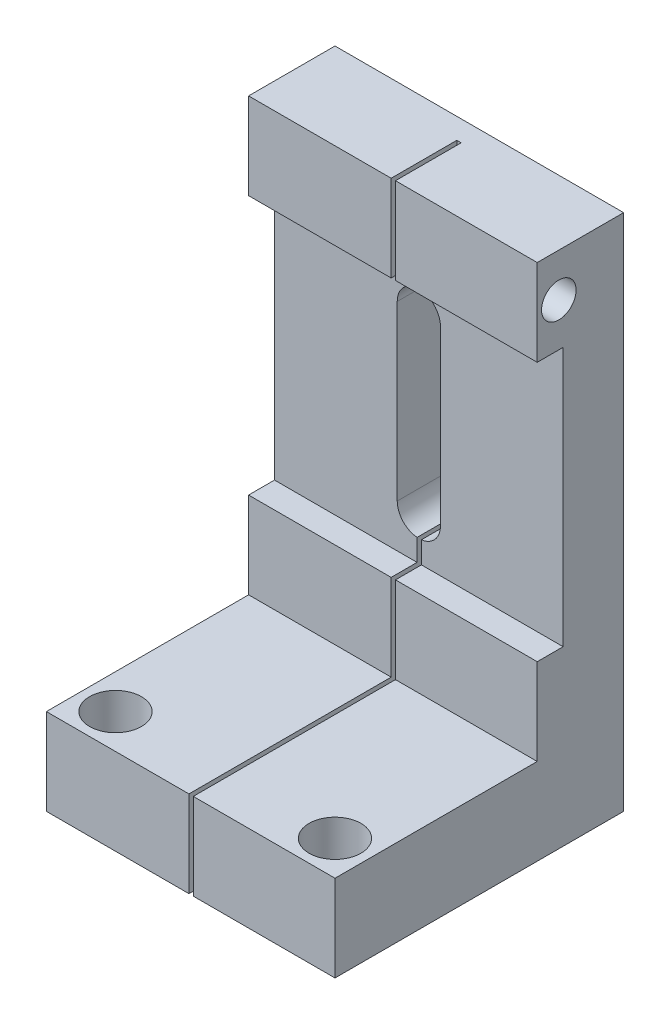
SolidWorks part; units mm, degrees
ref_plane "Front Plane" through (0, 0, 0) normal (0, 0, 1) x (1, 0, 0)
ref_plane "Top Plane" through (0, 0, 0) normal (0, 1, 0) x (1, 0, 0)
ref_plane "Right Plane" through (0, 0, 0) normal (1, 0, 0) x (0, 0, -1)
sketch "Sketch1" plane through (0, 0, 0) normal (0, 0, 1) x (1, 0, 0)
  line L1 (0, 0) -> (-33.4, 0)
  line L2 (0, 0) -> (0, -60)
  line L3 (0, -60) -> (-33.4, -60)
  line L4 (-33.4, 0) -> (-33.4, -60)
  dimension "D1" = 33.4
  dimension "D2" = 60
extrude "Boss-Extrude1" add sketch "Sketch1" along normal blind 10
sketch "Sketch2" plane through (0, 0, 10) normal (0, 0, 1) x (1, 0, 0)
  line L0 (-16.7, -15) -> (-16.7, -35) construction
  line L1 (-14.2, -15) -> (-14.2, -35)
  line L2 (-19.2, -15) -> (-19.2, -35)
  line L3 (0, -60) -> (0, 0) construction
  line L4 (-33.4, -60) -> (0, -60) construction
  arc A0 (-14.2, -15) -> (-19.2, -15) centre (-16.7, -15) ccw
  arc A1 (-19.2, -35) -> (-14.2, -35) centre (-16.7, -35) ccw
  point P2 (-16.7, -25)
  dimension "D1" = 5
  dimension "D2" = 20
  dimension "D3" = 16.7
  dimension "D4" = 35
extrude "Cut-Extrude1" cut sketch "Sketch2" against normal through all
sketch "Sketch5" plane through (0, 0, 0) normal (1, 0, 0) x (0, 0, -1)
  line L0 (-7, -10) -> (-10, -10)
  line L1 (-10, -60) -> (-10, 0) construction
  line L2 (-7, -10) -> (-7, -40)
  line L3 (-10, -60) -> (0, -60) construction
  line L4 (-7, -40) -> (-10, -40)
  line L7 (-10, -10) -> (-10, -40)
  dimension "D1" = 3
  dimension "D4" = 30
  dimension "D5" = 20
extrude "Cut-Extrude4" cut sketch "Sketch5" against normal through all
sketch "Sketch6" plane through (0, 0, 10) normal (0, 0, 1) x (1, 0, 0)
  line L0 (-33.4, -40) -> (-33.4, -60) construction
  line L1 (0, -60) -> (-33.4, -60)
  line L2 (0, -60) -> (0, -50)
  line L3 (0, -50) -> (-33.4, -50)
  line L4 (-33.4, -60) -> (-33.4, -50)
  dimension "D1" = 10
extrude "Boss-Extrude2" add sketch "Sketch6" along normal blind 23.4
sketch "Sketch7" plane through (0, -50, 0) normal (0, 1, 0) x (1, 0, 0)
  line L3 (-33.4, -33.4) -> (-33.4, -10) construction
  circle A0 centre (2.475, -15.1829) radius 2
  circle A1 centre (-29.275, -15.1829) radius 2
  dimension "D1" = 4
  dimension "D2" = 4
  dimension "D3" = 4.125
  dimension "D5" = 31.75
extrude "Cut-Extrude5" [suppressed] cut sketch "Sketch7" against normal blind 40
sketch "Sketch8" plane through (0, 0, 0) normal (0, 1, 0) x (1, 0, 0)
  line L2 (-16.9, -33.4) -> (-16.4, -33.4)
  line L5 (-16.9, -33.4) -> (-16.9, -2.4)
  line L7 (0, -33.4) -> (-33.4, -33.4) construction
  line L9 (-16.9, -2.4) -> (-16.4, -2.4)
  line L10 (-16.4, -33.4) -> (-16.4, -2.4)
  line L11 (-19.2, 0) -> (-19.2, -7) construction
  dimension "D1" = 0.5
  dimension "D2" = 2.3
  dimension "D3" = 31
extrude "Cut-Extrude7" cut sketch "Sketch8" against normal up to surface (60 mm away) up to face at (-16.7, -60, 16.7)
sketch "Sketch9" plane through (0, -60, 0) normal (0, -1, 0) x (1, 0, 0)
  line L3 (0, 33.4) -> (0, 0) construction
  line L5 (-33.4, 7) -> (-16.9, 7) construction
  circle A0 centre (-32.7, 5) radius 2
  circle A1 centre (-7.3, 5) radius 2
  dimension "D1" = 4
  dimension "D3" = 7.3
  dimension "D4" = 4
  dimension "D2" = 25.4
extrude "Cut-Extrude9" [suppressed] cut sketch "Sketch9" against normal blind 15
sketch "Sketch10" plane through (0, 0, 0) normal (1, 0, 0) x (0, 0, -1)
  line L1 (-10, 0) -> (0, 0) construction
  line L2 (-10, -10) -> (-10, 0) construction
  circle A0 centre (-7.5, -5) radius 2
  dimension "D1" = 4
  dimension "D2" = 5
  dimension "D3" = 2.5
extrude "Cut-Extrude10" cut sketch "Sketch10" against normal blind 30
sketch "Sketch12" plane through (0, -60, 0) normal (0, -1, 0) x (1, 0, 0)
  line L2 (-33.4, 33.4) -> (-16.9, 33.4) construction
  line L3 (-33.4, 33.4) -> (-33.4, 0) construction
  circle A0 centre (-29.4, 29.4) radius 3
  circle A1 centre (-4, 29.4) radius 3
  circle A2 centre (-4, 4) radius 3
  circle A3 centre (-29.4, 4) radius 3
  dimension "D1" = 6
  dimension "D2" = 4
  dimension "D3" = 4
  dimension "D4" = 2
  dimension "D5" = 2
extrude "Cut-Extrude11" cut sketch "Sketch12" against normal up to surface (10 mm away) up to face at (-8.2, -50, 21.7)
equation "\"inch\"=25.4"
equation "\"D5@Sketch7\"=\"inch\"*1.25"
equation "\"D2@Sketch9\"=\"inch\""
